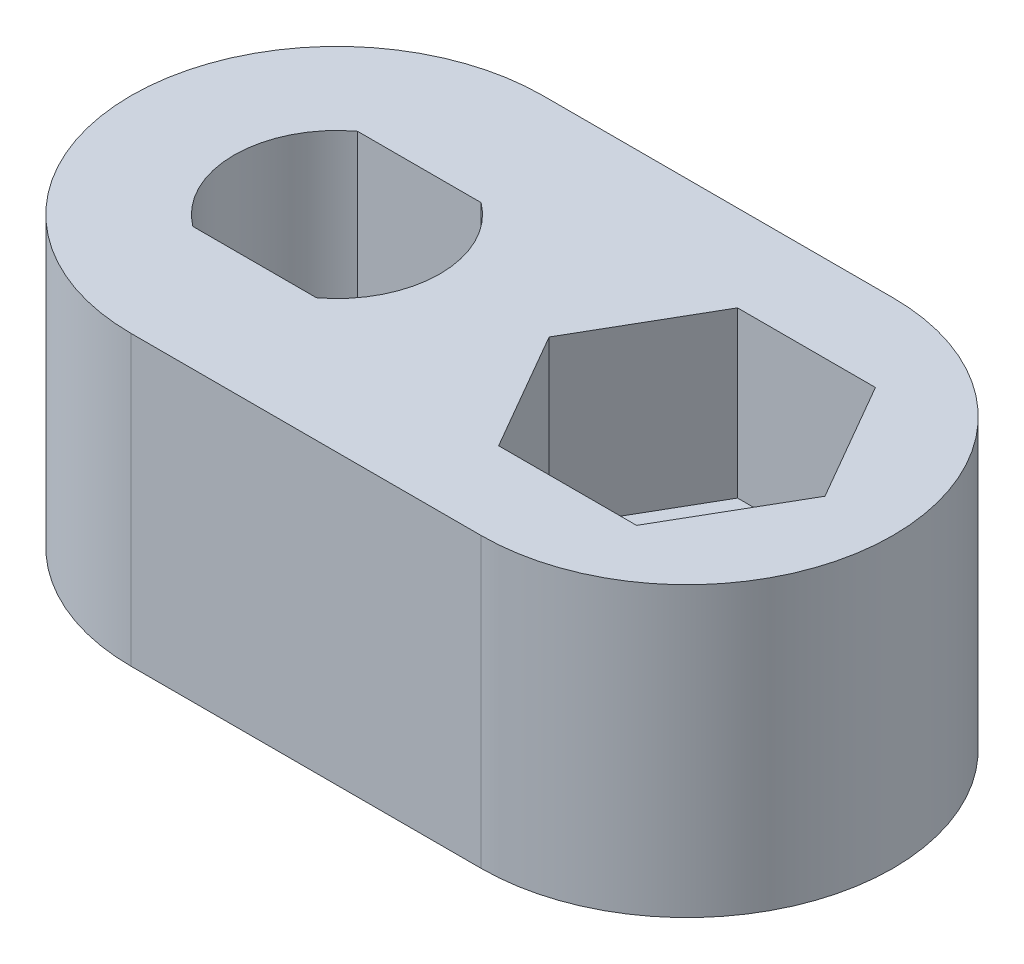
SolidWorks part; units mm, degrees
ref_plane "Front Plane" through (0, 0, 0) normal (0, 0, 1) x (1, 0, 0)
ref_plane "Top Plane" through (0, 0, 0) normal (0, 1, 0) x (1, 0, 0)
ref_plane "Right Plane" through (0, 0, 0) normal (1, 0, 0) x (0, 0, -1)
sketch "Sketch1" plane through (0, 0, 0) normal (0, 1, 0) x (1, 0, 0)
  line L0 (0, 0) -> (8.5, 0) construction
  line L1 (0, 5) -> (8.5, 5)
  line L2 (0, -5) -> (8.5, -5)
  arc A0 (0, 5) -> (0, -5) centre (0, 0) ccw
  arc A1 (8.5, -5) -> (8.5, 5) centre (8.5, 0) ccw
  point P3 (4.25, 0)
  dimension "D1" = 8.5
  dimension "D2" = 10
extrude "Boss-Extrude1" add sketch "Sketch1" along normal blind 7
sketch "Sketch2" plane through (0, 7, 0) normal (0, 1, 0) x (1, 0, 0)
  line L0 (-1.5, -2) -> (1.5, -2)
  line L1 (-1.5, 2) -> (1.5, 2)
  line L2 (0, 0) -> (-3.1448, 0) construction
  circle A0 centre (0, 0) radius 2.5
  dimension "D2" = 5
  dimension "D1" = 4
extrude "Cut-Extrude1" cut sketch "Sketch2" against normal blind 4 contours L0 A0 L1 region at (0, 7, 0)
hole_wizard "CSK for M3 Hex Socket Countersunk Cap Screw2" positions "Sketch8" profile "Sketch7" countersink size "M3" standard "ISO"
sketch "Sketch8" plane through (0, 0, 0) normal (0, -1, 0) x (-1, 0, 0)
  point P0 (0, 0)
sketch "Sketch7" plane through (0, 0, 0) normal (1, 0, 0) x (0, 0, -1)
  line L0 (0, 0) -> (0, 8.5215)
  line L1 (0, 8.5215) -> (1.7, 7.5)
  line L2 (1.7, 7.5) -> (1.7, 1.66)
  line L3 (1.7, 1.66) -> (3.36, 0)
  line L5 (3.36, 0) -> (0, 0)
  line L6 (-1.7, 1.66) -> (-3.36, 0) construction
  line L10 (0, 8.5215) -> (-1.7, 7.5) construction
  line L11 (0, -6.35) -> (0, 107.95) construction
  dimension "Hole Dia." = 3.4
  dimension "Hole Depth" = 7.5
  dimension "Near C'Sink Dia." = 6.72
  dimension "Near C'Sink Angle" = 90
  dimension "Drill Angle" = 118
hole_wizard "Hole1" positions "Sketch9" profile "Sketch10" legacy end condition through all
sketch "Sketch9" plane through (0, 0, 0) normal (0, -1, 0) x (-1, 0, 0)
  point P0 (-8.5, 0)
sketch "Sketch10" plane through (8.5, 0, 0) normal (1, 0, 0) x (0, 0, -1)
  line L0 (0, 0) -> (0, 7)
  line L1 (0, 7) -> (2.075, 7)
  line L2 (2.075, 7) -> (2.075, 0)
  line L3 (2.075, 0) -> (0, 0)
  line L4 (0, 110) -> (0, -10) construction
  dimension "Diameter" = 4.15
  dimension "Depth" = 7
sketch "Sketch11" plane through (0, 7, 0) normal (0, 1, 0) x (1, 0, 0)
  line L0 (8.5, 5) -> (0, 5) construction
  line L1 (11.8486, 0) -> (10.1743, 2.9)
  line L2 (10.1743, 2.9) -> (6.8257, 2.9)
  line L3 (6.8257, 2.9) -> (5.1514, 0)
  line L4 (5.1514, 0) -> (6.8257, -2.9)
  line L5 (6.8257, -2.9) -> (10.1743, -2.9)
  line L6 (10.1743, -2.9) -> (11.8486, 0)
  circle A0 centre (8.5, 0) radius 2.9 construction
  dimension "D1" = 5.8
extrude "Cut-Extrude2" cut sketch "Sketch11" against normal blind 4
